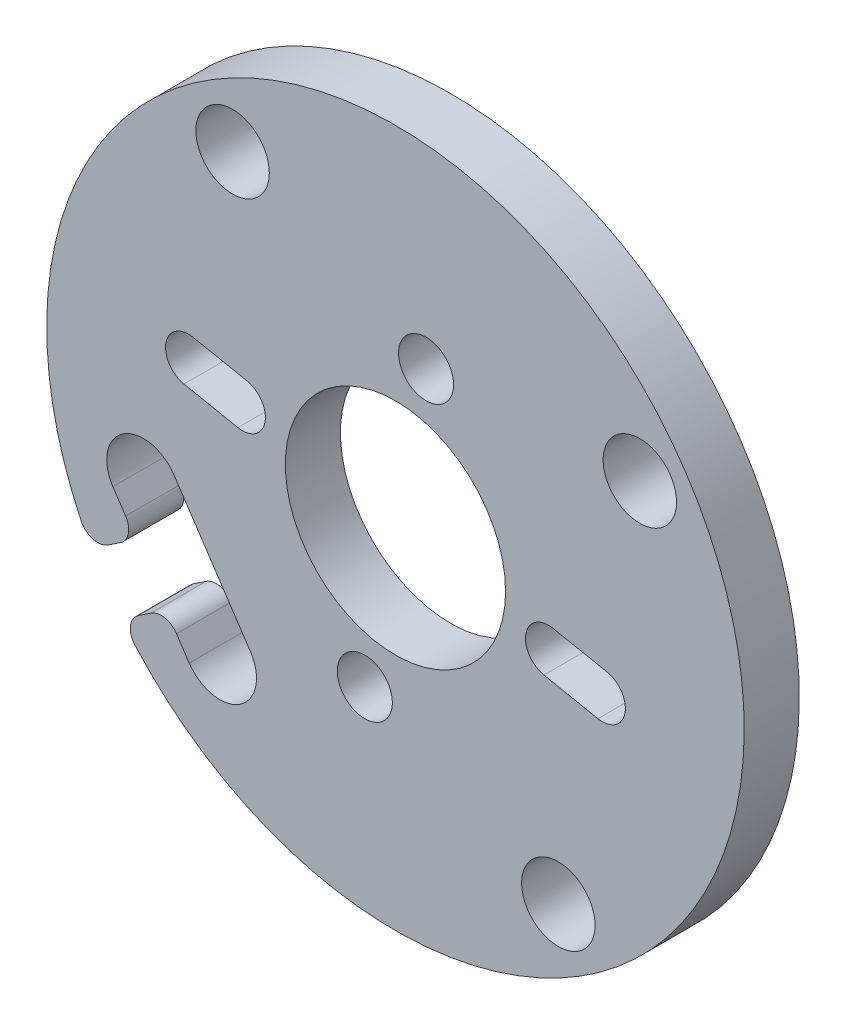
SolidWorks part; units mm, degrees
ref_plane "Front Plane" through (0, 0, 0) normal (0, 0, 1) x (1, 0, 0)
ref_plane "Top Plane" through (0, 0, 0) normal (0, 1, 0) x (1, 0, 0)
ref_plane "Right Plane" through (0, 0, 0) normal (1, 0, 0) x (0, 0, -1)
sketch "Sketch1" plane through (0, 0, 0) normal (0, 0, 1) x (1, 0, 0)
  line L0 (-8.8736, 13.3139) -> (8.8736, -13.3139) construction
  line L1 (1.668, 8.3347) -> (0, 0) construction
  line L2 (0, 0) -> (-11.2764, 2.2567) construction
  line L3 (-11.2764, 2.2567) -> (-8.3347, 1.668) construction
  line L4 (-11.0311, 3.4824) -> (-8.0894, 2.8937)
  line L5 (-11.5217, 1.031) -> (-8.58, 0.4423)
  line L6 (11.2762, -2.2577) -> (8.3346, -1.6687) construction
  line L7 (11.0308, -3.4834) -> (8.0892, -2.8944)
  line L8 (11.5216, -1.032) -> (8.58, -0.4431)
  line L9 (-13.7294, -4.6439) -> (-9.5699, -10.8848) construction
  line L10 (-12.0652, -3.5347) -> (-7.9057, -9.7756)
  line L11 (-15.3936, -5.7531) -> (-14.7004, -6.7933)
  line L12 (-11.6497, -7.7644) -> (0, 0) construction
  line L13 (-14.9779, -8.18) -> (-15.6649, -8.6378)
  line L14 (-11.9274, -10.9539) -> (-11.2342, -11.994)
  line L15 (-14.0011, -11.1342) -> (-13.3141, -10.6763)
  circle A1 centre (-8.8736, 13.3139) radius 2
  circle A2 centre (13.3139, 8.8736) radius 2
  circle A3 centre (8.8736, -13.3139) radius 2
  circle A4 centre (0, 0) radius 6
  circle A5 centre (-13.3139, -8.8736) radius 2 [skipped]
  circle A6 centre (1.668, 8.3347) radius 1.5
  circle A7 centre (-1.668, -8.3347) radius 1.5
  arc A8 (-11.0311, 3.4824) -> (-11.5217, 1.031) centre (-11.2764, 2.2567) ccw
  arc A9 (-8.58, 0.4423) -> (-8.0894, 2.8937) centre (-8.3347, 1.668) ccw
  arc A10 (11.0308, -3.4834) -> (11.5216, -1.032) centre (11.2762, -2.2577) ccw
  arc A11 (8.58, -0.4431) -> (8.0892, -2.8944) centre (8.3346, -1.6687) ccw
  arc A12 (-12.0652, -3.5347) -> (-15.3936, -5.7531) centre (-13.7294, -4.6439) ccw
  arc A13 (-11.2342, -11.994) -> (-7.9057, -9.7756) centre (-9.5699, -10.8848) ccw
  arc A14 (-11.9274, -10.9539) -> (-13.3141, -10.6763) centre (-12.7595, -11.5085) ccw
  arc A15 (-14.9779, -8.18) -> (-14.7004, -6.7933) centre (-15.5325, -7.3479) ccw
  arc A16 (-14.1935, -12.6311) -> (-14.0011, -11.1342) centre (-13.4465, -11.9663) cw
  arc A17 (-17.1205, -8.2394) -> (-15.6649, -8.6378) centre (-16.2195, -7.8057) ccw
  arc A19 (-14.1935, -12.6311) -> (-17.1205, -8.2394) centre (0, 0) ccw
  point P14 (0, 0)
  point P20 (0, 0)
  point P21 (-9.8056, 1.9624)
  point P28 (-11.6497, -7.7644)
  point P31 (9.8054, -1.9632)
  point P36 (0, 0)
  dimension "D4" = 12
  dimension "D5" = 3
  dimension "D6" = 4
  dimension "D20" = 1
  dimension "D21" = 1.5
  dimension "D22" = 1
  dimension "D2" = 16
  dimension "D8" = 8.5
  dimension "D9" = 45
  dimension "D10" = 45
  dimension "D11" = 3
  dimension "D12" = 2.5
  dimension "D14" = 10
  dimension "D15" = 10
  dimension "D16" = 7.5
  dimension "D17" = 4
  dimension "D18" = 14
  dimension "D19" = 3
  dimension "D3" = 4
  dimension "D7" = 2
  dimension "D13" = 2
extrude "Boss-Extrude1" add sketch "Sketch1" along normal blind 3
equation "\"D8@Sketch1\"=17/2"
equation "\"D14@Sketch1\"=20/2"
